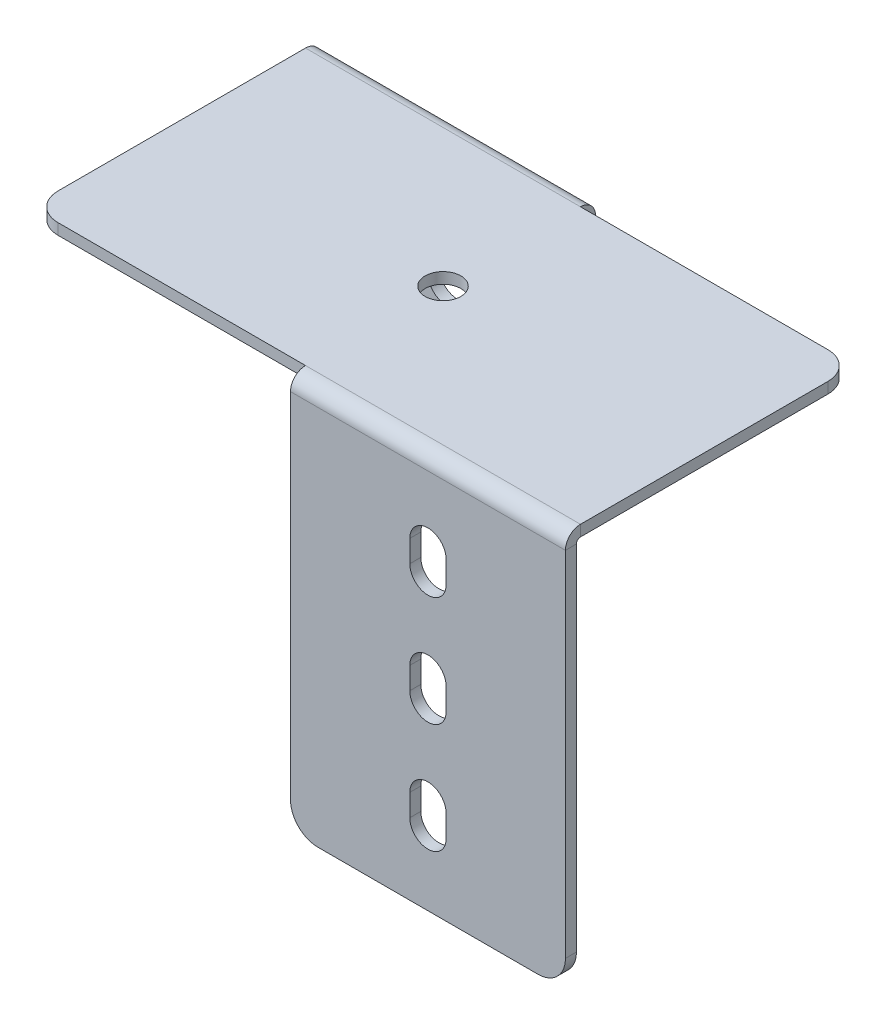
SolidWorks part; units mm, degrees
note: The reader was unsure of these and kept them because the rebuilt part matched: flange length of "Edge-Flange1", "Edge-Flange2".
ref_plane "Front Plane" through (0, 0, 0) normal (0, 0, 1) x (1, 0, 0)
ref_plane "Top Plane" through (0, 0, 0) normal (0, 1, 0) x (1, 0, 0)
ref_plane "Right Plane" through (0, 0, 0) normal (1, 0, 0) x (0, 0, -1)
sketch "Sketch1" plane through (0, 0, 0) normal (0, 1, 0) x (1, 0, 0)
  line L1 (-50, -25) -> (50, -25)
  line L2 (-50, -25) -> (-50, 25)
  line L3 (-50, 25) -> (50, 25)
  line L4 (50, -25) -> (50, 25)
  line L5 (-50, -25) -> (50, 25) construction
  line L6 (-50, 25) -> (50, -25) construction
  point P0 (0, 0)
  dimension "D1" = 100
  dimension "D2" = 50
base flange "Base-Flange1" sketch "Sketch1" thickness 2 reverse thickness direction no parameters "D1"=0.7366
sketch "Sketch8" plane through (0, 0, 0) normal (0, 1, 0) x (1, 0, 0)
  circle A0 centre (0, 0) radius 3.25
  dimension "D1" = 6.5
extrude "Cut-Extrude1" cut sketch "Sketch8" against normal through all normal cut yes
edge flange "Edge-Flange1" sketch "Sketch11" flange angle 90 flange length 72 flange position bend outside bend radius 0.7366 thickness 2 parameters "D6"=10
sketch "Sketch11" plane through (0, -2, 25) normal (0, 0, 1) x (-1, 0, 0)
  line L0 (50, 0) -> (-50, 0) construction
  line L1 (0, 0) -> (-50, 0)
  line L2 (-50, 0) -> (-50, 70)
  line L3 (-50, 70) -> (0, 70)
  line L4 (0, 70) -> (0, 0)
  point P4 (-26.8732, 0)
  point P6 (-49.6763, 0)
  point P7 (10.5232, 0)
  dimension "D1" = 50
  dimension "D2" = 70
bend "EdgeBend1" bend radius 0.7366 bend angle 90 parameters "D5"=1
edge flange "Edge-Flange2" sketch "Sketch15" flange angle 90 flange length 40 flange position bend outside bend radius 0.7366 thickness 2 relief rectangular parameters "D6"=10
sketch "Sketch15" plane through (0, -2, -25) normal (0, 0, -1) x (1, 0, 0)
  line L0 (50, 0) -> (-50, 0) construction
  line L1 (0, 0) -> (-50, 0)
  line L2 (-50, 0) -> (-50, 38)
  line L3 (-50, 38) -> (0, 38)
  line L4 (0, 38) -> (0, 0)
  point P4 (50, 35.3683)
  point P5 (0, 0)
  dimension "D1" = 38
bend "EdgeBend2" bend radius 0.7366 bend angle 90 parameters "D5"=2
sketch "Sketch12" plane through (0, 0, 27.7366) normal (0, 0, 1) x (1, 0, 0)
  line L0 (25, -55) -> (25, -59) construction
  line L1 (28.3, -55) -> (28.3, -59)
  line L2 (21.7, -55) -> (21.7, -59)
  line L3 (25, -59) -> (25, -72) construction
  line L4 (0, -72) -> (50, -72) construction
  arc A0 (28.3, -55) -> (21.7, -55) centre (25, -55) ccw
  arc A1 (21.7, -59) -> (28.3, -59) centre (25, -59) ccw
  point P2 (25, -57)
  dimension "D1" = 3.3
  dimension "D2" = 4
  dimension "D3" = 15
extrude "Cut-Extrude2" cut sketch "Sketch12" against normal through all normal cut yes
sketch "Sketch16" plane through (0, 0, -27.7366) normal (0, 0, -1) x (-1, 0, 0)
  line L0 (25, -25) -> (25, -15) construction
  line L1 (21.5, -25) -> (21.5, -15)
  line L2 (28.5, -25) -> (28.5, -15)
  line L3 (25, -25) -> (25, -40) construction
  line L4 (0, -40) -> (50, -40) construction
  arc A0 (21.5, -25) -> (28.5, -25) centre (25, -25) ccw
  arc A1 (28.5, -15) -> (21.5, -15) centre (25, -15) ccw
  point P2 (25, -20)
  dimension "D2" = 3.5
  dimension "D1" = 10
  dimension "D3" = 20
extrude "Cut-Extrude3" cut sketch "Sketch16" against normal through all normal cut yes
pattern_linear "LPattern1" count 3 spacing 20 along (0, 1, 0) of "Cut-Extrude2"
fillet "Fillet1" radius 5 6 edges at (-50, -1, 25) (50, -1, -25) (0, -72, 26.7366) (50, -72, 26.7366) (-50, -40, -26.7366) (0, -40, -26.7366)
sketch "Bend-Lines1" [suppressed] plane through (0, 0, 0) normal (0, 1, 0) x (1, 0, 0)
sketch "Bounding-Box1" [suppressed] plane through (0, 0, 0) normal (0, 1, 0) x (1, 0, 0)
sheet metal parameters "Sheet-Metal1" thickness 2 parameters "D1"=0.7366
flat pattern "Flat-Pattern1" [suppressed]
sketch "Bend-Lines2" plane through (0, 0, 0) normal (0, 1, 0) x (1, 0, 0)
sketch3d "Bounding-Box2" [suppressed]
  line L0 (-50, 25, 0) -> (50, 25, 0) construction
  line L1 (-50, -25, 0) -> (50, -25, 0) construction
  line L2 (-50, 25, 0) -> (-50, -25, 0) construction
  line L3 (50, 25, 0) -> (50, -25, 0) construction
sheet metal parameters "Sheet-Metal2" thickness 2 parameters "D1"=0.7366
flat pattern "Flat-Pattern1"
sketch "Bend-Lines2" plane through (0, 0, 0) normal (0, 1, 0) x (1, 0, 0)
sketch3d "Bounding-Box2" [suppressed]
  line L0 (50, 25, 0) -> (-50, 25, 0) construction
  line L1 (50, -25, 0) -> (-50, -25, 0) construction
  line L2 (50, 25, 0) -> (50, -25, 0) construction
  line L3 (-50, 25, 0) -> (-50, -25, 0) construction
sheet metal parameters "Sheet-Metal3" thickness 2 parameters "D1"=0.7366
flat pattern "Flat-Pattern1"
sketch "Bend-Lines2" plane through (0, 0, 0) normal (0, 1, 0) x (1, 0, 0)
  line L0 (0, -26.3639) -> (50, -26.3639) construction
  line L1 (0, -26.3639) -> (50, -26.3639) construction
sketch3d "Bounding-Box2" [suppressed]
  line L0 (-50, -96.9912, 0) -> (-50, 25, 0) construction
  line L1 (50, -96.9912, 0) -> (50, 25, 0) construction
  line L2 (-50, -96.9912, 0) -> (50, -96.9912, 0) construction
  line L3 (-50, 25, 0) -> (50, 25, 0) construction
bend of the flat pattern "Flatten-<EdgeBend1>1"
sheet metal parameters "Sheet-Metal4" thickness 2 parameters "D1"=0.7366
flat pattern "Flat-Pattern1"
sketch "Bend-Lines2" plane through (0, 0, 0) normal (0, 1, 0) x (1, 0, 0)
  line L0 (0, -26.3639) -> (50, -26.3639) construction
  line L1 (0, -26.3639) -> (50, -26.3639) construction
  line L2 (0, 26.3639) -> (-50, 26.3639) construction
  line L3 (0, 26.3639) -> (-50, 26.3639) construction
sketch3d "Bounding-Box2" [suppressed]
  line L0 (-50, -96.9912, 0) -> (-50, 64.9912, 0) construction
  line L1 (50, -96.9912, 0) -> (50, 64.9912, 0) construction
  line L2 (-50, -96.9912, 0) -> (50, -96.9912, 0) construction
  line L3 (-50, 64.9912, 0) -> (50, 64.9912, 0) construction
bend of the flat pattern "Flatten-<EdgeBend1>1"
bend of the flat pattern "Flatten-<EdgeBend2>2"
sheet metal parameters "Sheet-Metal5" thickness 2 parameters "D1"=0.7366
flat pattern "Flat-Pattern1"
sketch "Bend-Lines2" plane through (0, 0, 0) normal (0, 1, 0) x (1, 0, 0)
  line L0 (0, -26.3639) -> (50, -26.3639) construction
  line L1 (0, -26.3639) -> (50, -26.3639) construction
  line L2 (0, 26.3639) -> (-50, 26.3639) construction
  line L3 (0, 26.3639) -> (-50, 26.3639) construction
sketch3d "Bounding-Box2" [suppressed]
  line L0 (50.0001, -96.9912, 0) -> (50, 64.9913, 0) construction
  line L1 (-49.9999, -96.9913, 0) -> (-50, 64.9912, 0) construction
  line L2 (50.0001, -96.9912, 0) -> (-49.9999, -96.9913, 0) construction
  line L3 (50, 64.9913, 0) -> (-50, 64.9912, 0) construction
bend of the flat pattern "Flatten-<EdgeBend1>1"
bend of the flat pattern "Flatten-<EdgeBend2>3"
sheet metal parameters "Sheet-Metal6" thickness 2 parameters "D1"=0.7366
flat pattern "Flat-Pattern1"
sketch "Bend-Lines2" plane through (0, 0, 0) normal (0, 1, 0) x (1, 0, 0)
  line L0 (0, -26.3639) -> (50, -26.3639) construction
  line L1 (0, -26.3639) -> (50, -26.3639) construction
  line L2 (0, 26.3639) -> (-50, 26.3639) construction
  line L3 (0, 26.3639) -> (-50, 26.3639) construction
sketch3d "Bounding-Box2" [suppressed]
  line L0 (-50, -96.9912, 0) -> (-50, 64.9912, 0) construction
  line L1 (50, -96.9912, 0) -> (50, 64.9912, 0) construction
  line L2 (-50, -96.9912, 0) -> (50, -96.9912, 0) construction
  line L3 (-50, 64.9912, 0) -> (50, 64.9912, 0) construction
bend of the flat pattern "Flatten-<EdgeBend1>1"
bend of the flat pattern "Flatten-<EdgeBend2>1"
sheet metal parameters "Sheet-Metal7" thickness 2 parameters "D1"=0.7366
flat pattern "Flat-Pattern1"
sketch "Bend-Lines2" plane through (0, 0, 0) normal (0, 1, 0) x (1, 0, 0)
  line L0 (0, -26.3639) -> (50, -26.3639) construction
  line L1 (0, -26.3639) -> (50, -26.3639) construction
  line L2 (0, 26.3639) -> (-50, 26.3639) construction
  line L3 (0, 26.3639) -> (-50, 26.3639) construction
sketch3d "Bounding-Box2" [suppressed]
  line L0 (-50, -96.9912, 0) -> (-50, 64.9912, 0) construction
  line L1 (50, -96.9912, 0) -> (50, 64.9912, 0) construction
  line L2 (-50, -96.9912, 0) -> (50, -96.9912, 0) construction
  line L3 (-50, 64.9912, 0) -> (50, 64.9912, 0) construction
bend of the flat pattern "Flatten-<EdgeBend1>1"
bend of the flat pattern "Flatten-<EdgeBend2>2"
